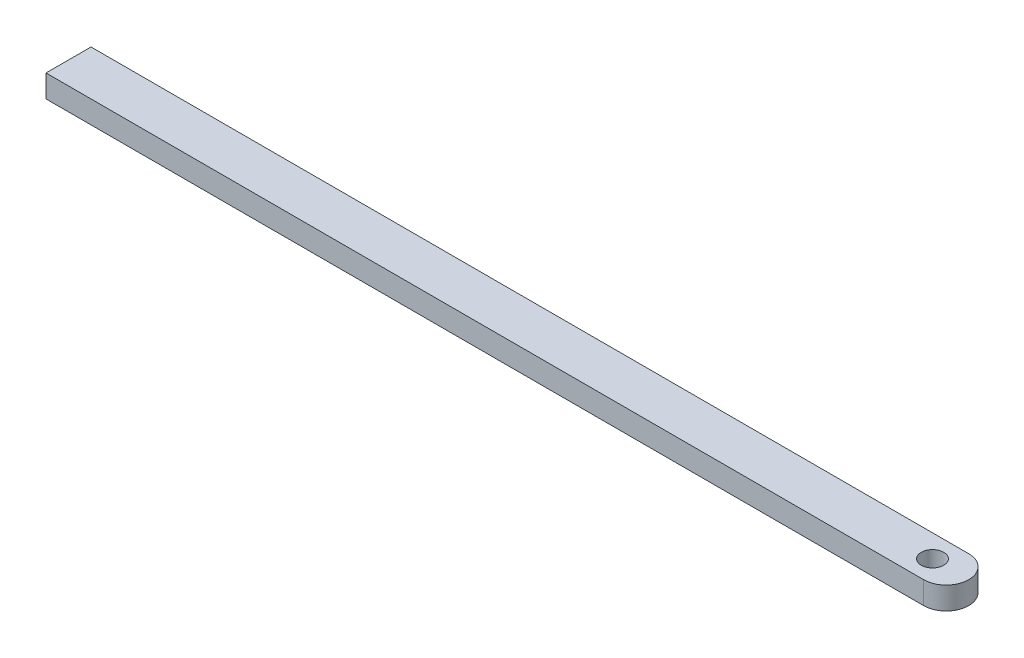
SolidWorks part; units mm, degrees
ref_plane "Front Plane" through (0, 0, 0) normal (0, 0, 1) x (1, 0, 0)
ref_plane "Top Plane" through (0, 0, 0) normal (0, 1, 0) x (1, 0, 0)
ref_plane "Right Plane" through (0, 0, 0) normal (1, 0, 0) x (0, 0, -1)
sketch "Sketch2" plane through (0, 0, 0) normal (0, 1, 0) x (1, 0, 0)
  line L0 (-110.9556, -13.6733) -> (289.0444, -13.6733) construction
  line L1 (-110.9556, -3.6733) -> (289.0444, -3.6733)
  line L2 (-110.9556, -3.6733) -> (-110.9556, -23.6733)
  line L3 (-110.9556, -23.6733) -> (289.0444, -23.6733)
  line L4 (289.0444, -3.6733) -> (289.0444, -23.6733)
  circle A0 centre (272.9337, -13.6733) radius 5
  point P8 (272.9337, -13.6733)
  dimension "D2" = 10
  dimension "D1" = 400
  dimension "D3" = 20
extrude "Boss-Extrude1" add sketch "Sketch2" along normal blind 10
fillet "Fillet1" 2 edges at (289.0444, 5, 3.6733) (289.0444, 5, 23.6733) type full round first side face at (89.0444, 5, 3.6733) second side face at (89.0444, 5, 23.6733) middle face at (289.0444, 5, 13.6733)
